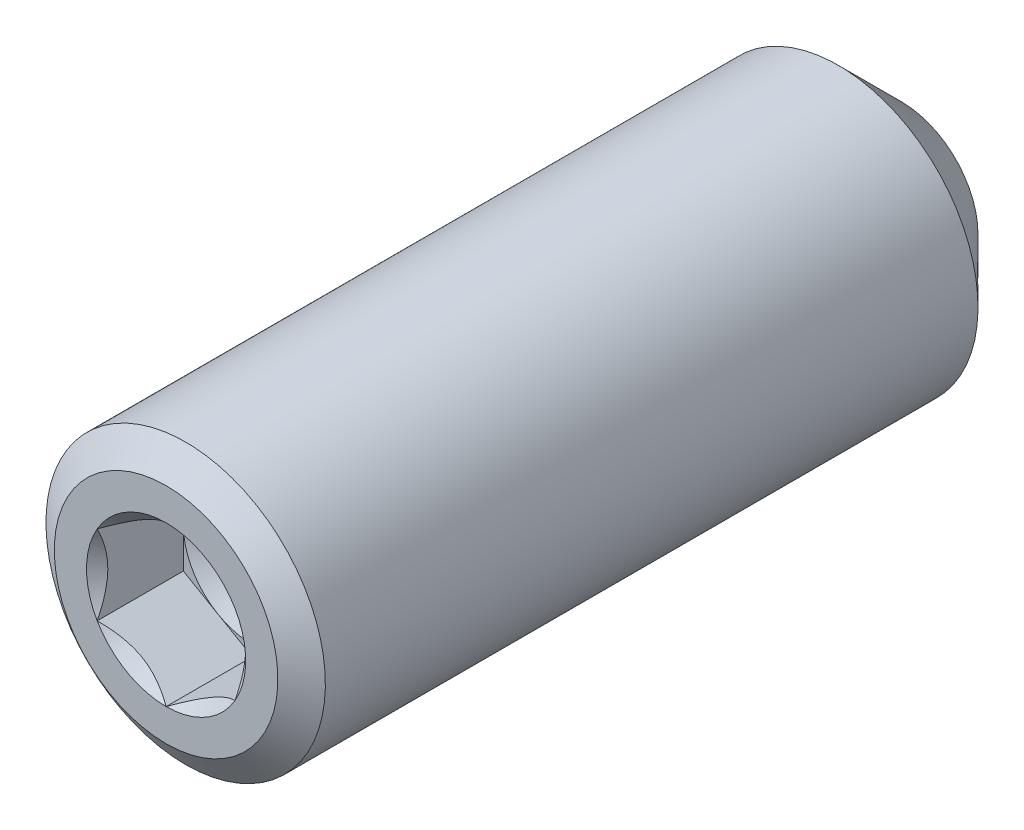
SolidWorks part; units mm, degrees
ref_plane "Front" through (0, 0, 0) normal (0, 0, 1) x (1, 0, 0)
ref_plane "Top" through (0, 0, 0) normal (0, 1, 0) x (1, 0, 0)
ref_plane "Right" through (0, 0, 0) normal (1, 0, 0) x (0, 0, -1)
sketch "Sketch22" plane through (0, 0, 0) normal (1, 0, 0) x (0, 0, -1)
  line L0 (-5.9528, 0) -> (-5.9528, 1.9304)
  line L1 (-5.9528, 1.9304) -> (-5.6148, 2.413)
  line L2 (-5.6148, 2.413) -> (5.6565, 2.413)
  line L3 (5.6565, 2.413) -> (6.7472, 1.3222)
  line L4 (6.7472, 1.3222) -> (5.9528, 0)
  line L5 (5.9528, 0) -> (-5.9528, 0)
  line L6 (5.9528, 0) -> (6.7472, 0) construction
  line L7 (6.7472, 0) -> (6.7472, 1.3222) construction
  line L8 (6.7472, -1.3222) -> (5.9528, 0) construction
  line L9 (-5.6148, -2.413) -> (5.6565, -2.413) construction
  dimension "Dia" = 4.826
  dimension "Length" = 12.7
  dimension "D3" = 35
  dimension "D5" = 118
  dimension "D6" = 45
  dimension "D7" = 3.8608
revolve "Revolve1" add sketch "Sketch22" angle 360 about L6
ref_plane "Plane1" through (0, 0, -6.7472) normal (0, 0, 1) x (1, 0, 0)
sketch "Sketch27" plane through (0, 0, -6.7472) normal (0, 0, 1) x (1, 0, 0)
  circle A0 centre (0, 0) radius 2.413 construction
  circle A1 centre (0, 0) radius 2.413
curve "Helix/Spiral1" [suppressed] pitch 1.0583 height 13.7583 turns 13
sketch "Sketch28" plane through (0, 0, 0) normal (1, 0, 0) x (0, 0, -1)
  line L0 (6.7472, 2.413) -> (7.6733, 2.413)
  line L1 (7.6733, 2.413) -> (7.2764, 1.7256)
  line L2 (7.2764, 1.7256) -> (7.1441, 1.7256)
  line L3 (7.1441, 1.7256) -> (6.7472, 2.413)
  line L4 (6.9457, 2.0693) -> (7.4748, 2.0693) construction
  line L6 (-5.6148, 2.413) -> (5.6565, 2.413) construction
  line L7 (6.7472, 2.6543) -> (6.7472, -2.6543) construction
  dimension "D1" = 0.1323
  dimension "D3" = 60
  dimension "D2" = 0.5292
sweep "Cut-Sweep2" [suppressed] cut profiles "Sketch28" path "Helix/Spiral1"
sketch "Sketch23" plane through (0, 0, 5.9528) normal (0, 0, 1) x (1, 0, 0)
  line L1 (0, 1.3748) -> (-1.1906, 0.6874)
  line L2 (-1.1906, 0.6874) -> (-1.1906, -0.6874)
  line L3 (-1.1906, -0.6874) -> (0, -1.3748)
  line L4 (0, -1.3748) -> (1.1906, -0.6874)
  line L5 (1.1906, -0.6874) -> (1.1906, 0.6874)
  line L6 (1.1906, 0.6874) -> (0, 1.3748)
  circle A0 centre (0, 0) radius 1.1906 construction
  dimension "Hex" = 2.3813
extrude "Cut-Extrude10" cut sketch "Sketch23" against normal blind 1.4883
sketch "Sketch24" plane through (0, 0, 5.9528) normal (0, 0, 1) x (1, 0, 0)
  circle A0 centre (0, 0) radius 1.3748
extrude "Cut-Extrude11" cut sketch "Sketch24" against normal through all draft 45
sketch "Sketch26" plane through (0, 0, 4.4645) normal (0, 0, 1) x (1, 0, 0)
  circle A0 centre (0, 0) radius 1.1906 construction
  circle A1 centre (0, 0) radius 1.1906
extrude "Cut-Extrude12" cut sketch "Sketch26" against normal through all draft 60
sketch "Sketch30" plane through (0, 0, 0) normal (1, 0, 0) x (0, 0, -1)
  line L0 (-5.6148, 2.413) -> (5.6565, 2.413) construction
  line L1 (-5.9528, 0) -> (-5.9528, 1.9304) construction
  line L2 (6.7472, 0) -> (6.7472, 1.3222) construction
  line L3 (-5.6148, -2.413) -> (5.6565, -2.413) construction
  point P0 (-5.9528, 2.413)
  point P1 (6.7472, 2.413)
  point P2 (6.7472, -2.413)
  point P11 (4.1014, -2.413)
  dimension "D1" = 2.6458
sketch "Sketch31" plane through (0, 0, 0) normal (1, 0, 0) x (0, 0, -1)
  line L2 (5.9528, 0) -> (6.7472, -1.3222)
  line L3 (6.7472, 1.3222) -> (5.9528, 0)
equation "\"D7@Sketch22\"=\"Dia@Sketch22\"*.8"
equation "\"D1@Sketch28\" = \"D4@Helix/Spiral1\" * .125"
equation "\"D3@Helix/Spiral1\" = \"Length@Sketch22\" + \"D4@Helix/Spiral1\""
equation "\"D1@Sketch30\" = \"D4@Helix/Spiral1\" * 2.5"
equation "\"hex Depth@Cut-Extrude10\" = \"Hex@Sketch23\" * .625"
equation "\"D2@Sketch28\" = \"D4@Helix/Spiral1\" * .5"
